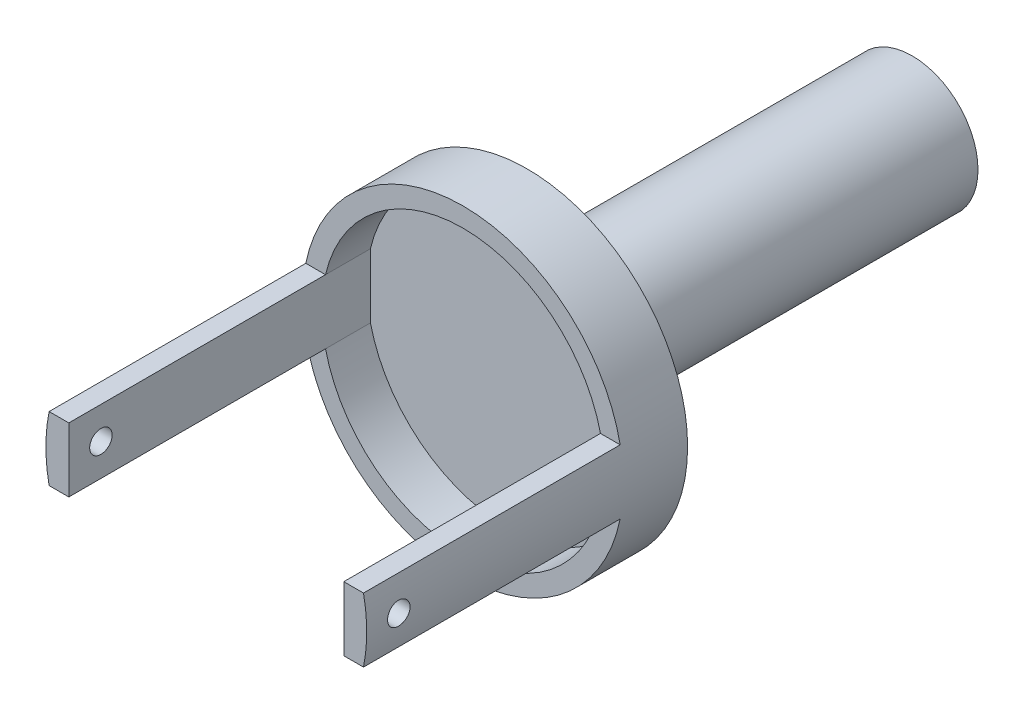
SolidWorks part; units mm, degrees
ref_plane "Front Plane" through (0, 0, 0) normal (0, 0, 1) x (1, 0, 0)
ref_plane "Top Plane" through (0, 0, 0) normal (0, 1, 0) x (1, 0, 0)
ref_plane "Right Plane" through (0, 0, 0) normal (1, 0, 0) x (0, 0, -1)
sketch "Sketch1" plane through (0, 0, 0) normal (0, 0, 1) x (1, 0, 0)
  circle A0 centre (0, 0) radius 25
  circle A1 centre (0, 0) radius 22
  dimension "D1" = 50
  dimension "D2" = 3
extrude "Boss-Extrude1" add sketch "Sketch1" along normal blind 10
extrude "Boss-Extrude2" add sketch "Sketch1<2>" along normal blind 3 contours A1
sketch "Sketch1<2>" plane through (0, 0, 0) normal (0, 0, 1) x (1, 0, 0) same geometry as "Sketch1"
sketch "Sketch2" plane through (0, 0, 10) normal (0, 0, 1) x (1, 0, 0)
  line L0 (-24.4949, 5) -> (-21.4243, 5)
  line L1 (-24.4949, -5) -> (-21.4243, -5)
  line L2 (21.4243, -5) -> (24.4949, -5)
  line L3 (21.4243, 5) -> (24.4949, 5)
  line L4 (-21.4243, -5) -> (-21.4243, 5)
  line L5 (21.4243, -5) -> (21.4243, 5)
  circle A0 centre (0, 0) radius 25 construction
  arc A3 (-24.4949, 5) -> (-24.4949, -5) centre (0, 0) ccw
  arc A4 (24.4949, -5) -> (24.4949, 5) centre (0, 0) ccw
  circle A7 centre (0, 0) radius 22 construction
  arc A8 (-21.4243, 5) -> (-21.4243, -5) centre (0, 0) ccw
  arc A9 (21.4243, -5) -> (21.4243, 5) centre (0, 0) ccw
  circle M5 centre (0, 0) radius 25
  circle M6 centre (0, 0) radius 22
  dimension "D1" = 10
extrude "Boss-Extrude3" add sketch "Sketch2" against normal up to surface (7 mm away) contours L4 M6 | L5 M6 region at (-21.6548, 0, 10) region at (21.6548, 0, 10) up to face at (22, 0, 3)
extrude "Boss-Extrude4" add sketch "Sketch2<4>" along normal blind 40 contours L1 L0 M5 M6 | L4 M6 | L5 M6 | L3 L2 M6 M5 region at (-23.3196, 0, 10) region at (-21.6548, 0, 10) region at (23.3196, 0, 10) region at (21.6548, 0, 10)
sketch "Sketch2<4>" plane through (0, 0, 10) normal (0, 0, 1) x (1, 0, 0) same geometry as "Sketch2"
sketch "Sketch3" plane through (-21.4243, 0, 0) normal (1, 0, 0) x (0, 0, -1)
  line L0 (-50, -5) -> (-50, 5) construction
  circle A0 centre (-45, 0) radius 1.75
  point P4 (-50, 0)
  dimension "D2" = 3.5
  dimension "D1" = 5
extrude "Cut-Extrude1" cut sketch "Sketch3" against normal up to surface and the other way up to surface up to face at (0, 0, 30) other way up to face at (0, 0, 30)
sketch "Sketch4" plane through (0, 0, 0) normal (0, 0, -1) x (-1, 0, 0)
  circle A0 centre (0, 0) radius 8.25
  circle A1 centre (0, 0) radius 10.25
  dimension "D1" = 16.5
  dimension "D2" = 20.5
extrude "Boss-Extrude5" add sketch "Sketch4" along normal blind 60
extrude "Boss-Extrude6" add sketch "Sketch4<2>" along normal blind 44 contours A0 region at (0, 0, 0)
sketch "Sketch4<2>" plane through (0, 0, 0) normal (0, 0, -1) x (-1, 0, 0) same geometry as "Sketch4"
